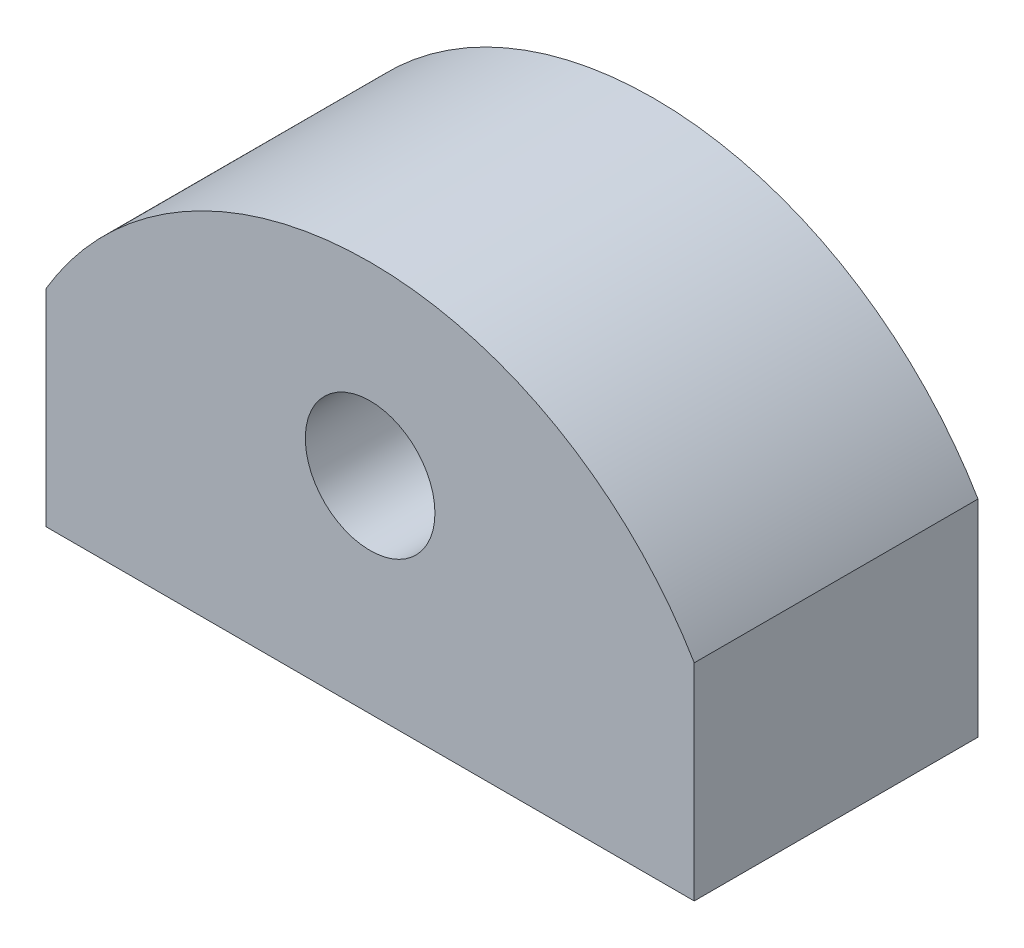
SolidWorks part; units mm, degrees
material "6061 Alloy"
ref_plane "Front Plane" through (0, 0, 0) normal (0, 0, 1) x (1, 0, 0)
ref_plane "Top Plane" through (0, 0, 0) normal (0, 1, 0) x (1, 0, 0)
ref_plane "Right Plane" through (0, 0, 0) normal (1, 0, 0) x (0, 0, -1)
sketch "Sketch1" plane through (0, 0, 0) normal (0, 0, 1) x (1, 0, 0)
  line L1 (-11, 3.5) -> (11, 3.5) construction
  line L2 (-11, 3.5) -> (-11, -3.5)
  line L3 (-11, -3.5) -> (11, -3.5)
  line L4 (11, 3.5) -> (11, -3.5)
  line L5 (0, -3.5) -> (0, -3) construction
  line L6 (-11, 0) -> (11, 0) construction
  arc A0 (-11, 3.5) -> (11, 3.5) centre (0, -3) cw
  point P0 (0, 0)
  dimension "D1" = 22
  dimension "D2" = 7
  dimension "D3" = 3
extrude "3/8" add sketch "Sketch1" along normal blind 9.63
sketch "Sketch2" plane through (0, 0, 9.63) normal (0, 0, 1) x (1, 0, 0)
  line L0 (-11, 3.5) -> (11, 3.5) construction
  circle A0 centre (0, 3.5) radius 2.2
  dimension "D1" = 4.4
extrude "M5_DRILL" cut sketch "Sketch2" against normal up to surface (9.63 mm away) up to face at (0, 1.5692, 0)
sketch "Sketch3" plane through (0, -3.5, 0) normal (0, -1, 0) x (1, 0, 0)
  line L0 (-11, 4.815) -> (11, 4.815) construction
  line L1 (-11, 9.63) -> (-11, 0) construction
  line L2 (11, 9.63) -> (11, 0) construction
  line L3 (0, 0) -> (0, 9.63) construction
  line L4 (-11, 9.63) -> (11, 9.63) construction
  circle A0 centre (-6, 4.815) radius 1.75
  circle A1 centre (6, 4.815) radius 1.75
  dimension "D1" = 3.5
  dimension "D2" = 6
extrude "M4_DRILL" cut sketch "Sketch3" against normal blind 8
